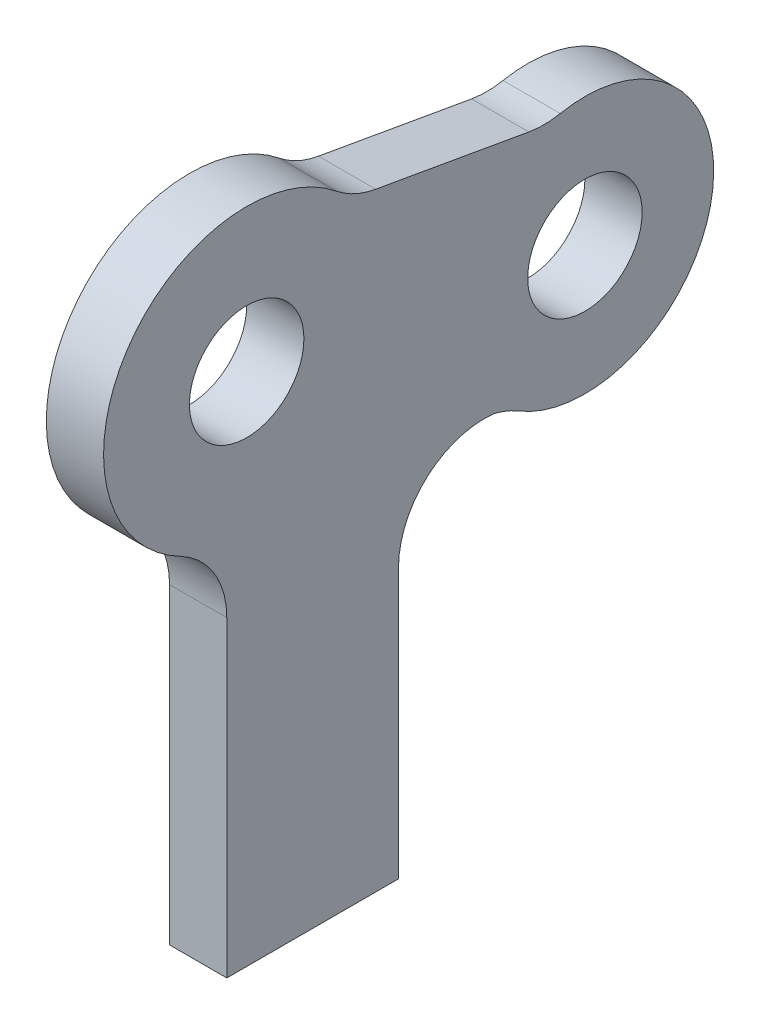
SolidWorks part; units mm, degrees
ref_plane "前视基准面" through (0, 0, 0) normal (0, 0, 1) x (1, 0, 0)
ref_plane "上视基准面" through (0, 0, 0) normal (0, 1, 0) x (1, 0, 0)
ref_plane "右视基准面" through (0, 0, 0) normal (1, 0, 0) x (0, 0, -1)
other "Configuration Table"
sketch "草图1" plane through (0, 0, 0) normal (1, 0, 0) x (0, 0, -1)
  line L1 (-0.6946, -3.9392) -> (5.3054, -3.9392)
  line L2 (-0.6946, -3.9392) -> (-0.6946, -18)
  line L3 (-0.6946, -18) -> (5.3054, -18)
  line L4 (5.3054, -3.9392) -> (5.3054, -18)
  line L5 (-0.6946, -3.9392) -> (11.1231, -6.023)
  line L6 (-0.6946, -3.9392) -> (0.6946, 3.9392)
  line L7 (0.6946, 3.9392) -> (12.5123, 1.8555)
  line L8 (11.1231, -6.023) -> (12.5123, 1.8555)
  circle A0 centre (0, 0) radius 5
  circle A1 centre (11.8177, -2.0838) radius 4.5
  circle A2 centre (0, 0) radius 2
  circle A3 centre (11.8177, -2.0838) radius 2
  dimension "D4" = 10
  dimension "D5" = 9
  dimension "D8" = 4
  dimension "D1" = 80
  dimension "D2" = 18
  dimension "D3" = 6
  dimension "D6" = 8
  dimension "D7" = 12
extrude "凸台-拉伸1" add sketch "草图1" along normal blind 2 contours L6 L7 L8 L5 | A0 | A1 | L1 L4 L3 L2
extrude "切除-拉伸3" cut sketch "草图1<3>" against normal through all and the other way through all contours A2 | A3
sketch "草图1<3>" plane through (0, 0, 0) normal (1, 0, 0) x (0, 0, -1) same geometry as "草图1"
fillet "圆角1" radius 3 5 edges at (1, -4.9515, 0.6946) (1, 3.4183, -3.649) (1, -4.9972, -5.3054) (1, -5.665, -9.0929) (1, 2.2134, -10.4821)
equation "\"JointPoint\"= 2mm"
